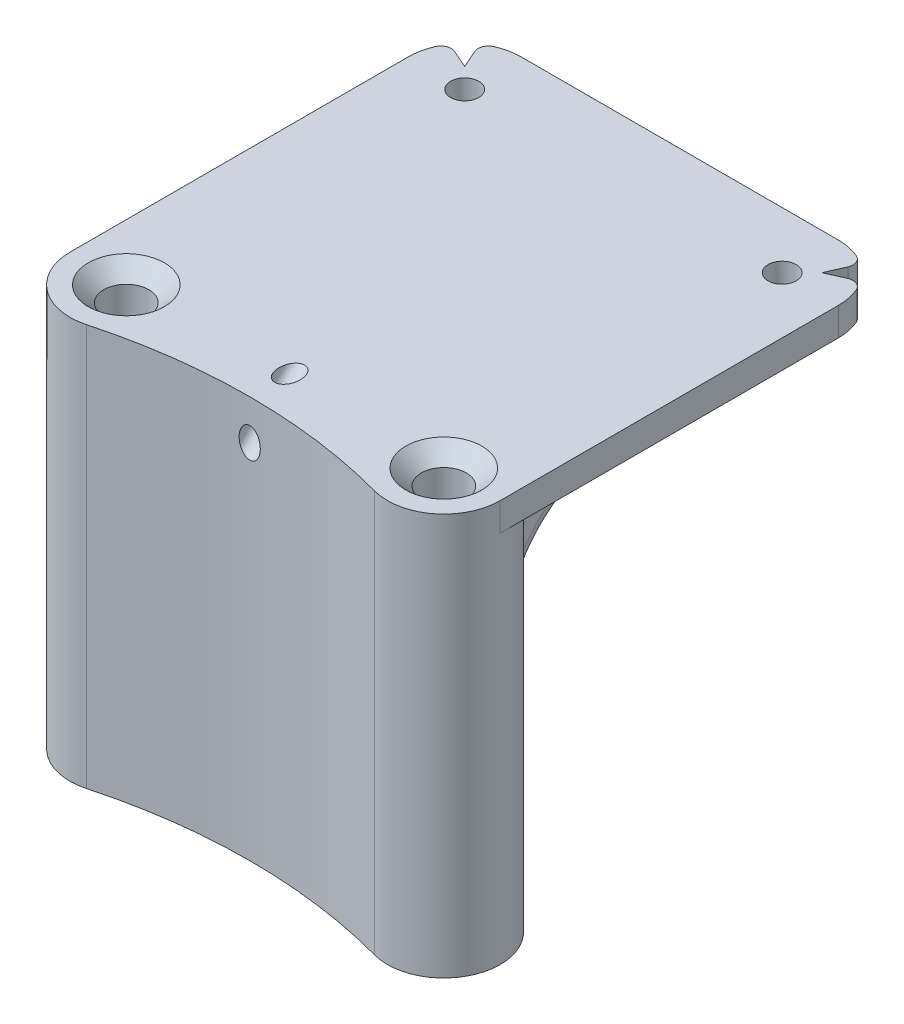
SolidWorks part; units mm, degrees
ref_plane "前视基准面" through (0, 0, 0) normal (0, 0, 1) x (1, 0, 0)
ref_plane "上视基准面" through (0, 0, 0) normal (0, 1, 0) x (1, 0, 0)
ref_plane "右视基准面" through (0, 0, 0) normal (1, 0, 0) x (0, 0, -1)
other "Configuration Table"
sketch "草图2" plane through (0, 0, 0) normal (0, 1, 0) x (1, 0, 0)
  line L0 (0, 41.5125) -> (0, -41.5125) construction
  line L1 (-11.26, 0) -> (11.26, 0) construction
  arc A0 (-10.2129, 3.8605) -> (-10.2129, -3.8605) centre (-11.26, 0) ccw
  arc A1 (10.2129, 3.8605) -> (10.2129, -3.8605) centre (11.26, 0) cw
  arc A2 (-10.2129, -3.8605) -> (10.2129, -3.8605) centre (0, -41.5125) cw
  arc A3 (-10.2129, 3.8605) -> (10.2129, 3.8605) centre (0, 41.5125) ccw
  point P1 (-2.8347, -1.5911)
  point P4 (0, -26.6736)
  point P5 (0, -26.6736)
  point P10 (0, 0)
  point P12 (-8.124, -6.199)
  point P13 (0, 0)
  point P14 (0, -13.3421)
  point P15 (6.0787, -3.7192)
  point P16 (-6.0424, -3.1641)
  point P17 (0, -18.5214)
  point P18 (0, -17.4888)
  point P19 (0, 0)
  point P20 (0, 0)
  point P21 (0, 0)
  point P22 (0, 0)
  point P25 (0, -26.6736)
  point P26 (0, -2.5)
  dimension "D1" = 4
  dimension "D2" = 22.52
  dimension "D3" = 2.5
extrude "凸台-拉伸1" add sketch "草图2" along normal blind 28.5
sketch "草图3" plane through (0, 0, 0) normal (0, -1, 0) x (1, 0, 0)
  line L3 (0, 2.5) -> (0, -2.5) construction
  line L5 (-15.26, 0) -> (15.26, 0) construction
  circle A0 centre (-11.26, 0) radius 1.6
  arc A2 (-10.2129, 3.8605) -> (10.2129, 3.8605) centre (0, 41.5125) ccw construction
  arc A3 (10.2129, -3.8605) -> (-10.2129, -3.8605) centre (0, -41.5125) ccw construction
  arc A4 (-10.2129, 3.8605) -> (-10.2129, -3.8605) centre (-11.26, 0) ccw construction
  arc A5 (10.2129, -3.8605) -> (10.2129, 3.8605) centre (11.26, 0) ccw construction
  circle A6 centre (11.26, 0) radius 1.6
  point P2 (0, 0)
  dimension "D1" = 3.2
extrude "切除-拉伸1" cut sketch "草图3" against normal through all
sketch "草图4" plane through (0, 28.5, 0) normal (0, 1, 0) x (1, 0, 0)
  line L0 (-11.26, 0) -> (11.26, 0) construction
  line L1 (0, -2.5) -> (0, 2.5) construction
  line L2 (-15.26, 0) -> (-15.26, 28)
  line L3 (-15.26, 28) -> (15.26, 28)
  line L5 (15.26, 0) -> (15.26, 28)
  arc A0 (10.2129, -3.8605) -> (-10.2129, -3.8605) centre (0, -41.5125) ccw construction
  arc A1 (-10.2129, 3.8605) -> (10.2129, 3.8605) centre (0, 41.5125) ccw construction
  arc A2 (-10.2129, 3.8605) -> (-10.2129, -3.8605) centre (-11.26, 0) ccw construction
  arc A3 (10.2129, -3.8605) -> (10.2129, 3.8605) centre (11.26, 0) ccw construction
  arc A7 (-15.26, 0) -> (-10.2129, 3.8605) centre (-11.26, 0) cw
  arc A8 (-10.2129, 3.8605) -> (10.2129, 3.8605) centre (0, 41.5125) ccw
  arc A9 (10.2129, 3.8605) -> (15.26, 0) centre (11.26, 0) cw
  dimension "D1" = 28
extrude "凸台-拉伸2" add sketch "草图4" against normal blind 2
sketch "草图5" plane through (0, 26.5, 0) normal (0, -1, 0) x (1, 0, 0)
  line L0 (15.26, -28) -> (-15.26, -28) construction
  line L1 (-10.26, -26) -> (-5.76, -26)
  line L2 (-10.26, -26) -> (-10.26, -28)
  line L3 (-10.26, -28) -> (-5.76, -28)
  line L4 (-5.76, -26) -> (-5.76, -28)
  line L5 (-15.26, -28) -> (-15.26, 0) construction
  dimension "D1" = 2
  dimension "D2" = 4.5
  dimension "D3" = 5
extrude "凸台-拉伸3" add sketch "草图5" along normal blind 15.5
sketch "草图6" plane through (0, 0, -28) normal (0, 0, -1) x (-1, 0, 0)
  line L0 (10.26, 11) -> (5.76, 11) construction
  line L1 (5.76, 11) -> (5.76, 26.5) construction
  circle A0 centre (7.81, 17) radius 1.5
  dimension "D1" = 3
  dimension "D2" = 6
  dimension "D3" = 2.05
extrude "切除-拉伸2" cut sketch "草图6" against normal up to next
chamfer "倒角1" distance 1.1 angle 45 2 edges at (-11.26, 28.5, -1.6) (11.26, 28.5, 1.6)
fillet "圆角1" radius 1 1 edges at (-10.26, 11, -27)
fillet "圆角3" radius 4 2 edges at (15.26, 27.5, -28) (-15.26, 27.5, -28)
fillet "圆角4" radius 5 1 edges at (-10.26, 26.5, -27)
ref_plane "基准面1" through (0, 28.25, -28.25) normal (0, 0.7071, -0.7071) x (-1, 0, 0)
sketch "草图9" plane through (0, 28.25, -28.25) normal (0, 0.7071, -0.7071) x (-1, 0, 0)
  circle A0 centre (0, 19.9203) radius 0.75
  ellipse E0 centre (0, 49.5063) end of major axis (-39.0125, 49.5063) minor radius 27.586 (-10.2129, 22.8823) -> (10.2129, 22.8823) ccw construction
  point P2 (0, 15.9481)
  point P10 (0, 0)
  dimension "D1" = 1.5
  dimension "D2" = 2
extrude "切除-拉伸4" cut sketch "草图9" against normal through all
sketch "草图10" plane through (0, 28.5, 0) normal (0, 1, 0) x (1, 0, 0)
  line L0 (0, 28) -> (0, -2.5) construction
  line L1 (11.26, 28) -> (-11.26, 28) construction
  line L2 (-11.26, 24) -> (-14.0884, 26.8284) construction
  line L3 (-12.6742, 25.4142) -> (-13.5079, 27.3086)
  line L4 (-12.6742, 25.4142) -> (-14.5686, 26.2479)
  line L5 (12.6742, 25.4142) -> (13.5079, 27.3086)
  line L6 (12.6742, 25.4142) -> (14.5686, 26.2479)
  arc A0 (10.2129, -3.8605) -> (-10.2129, -3.8605) centre (0, -41.5125) ccw construction
  circle A1 centre (-11.26, 24) radius 1
  circle A2 centre (11.26, 24) radius 1
  arc A3 (-11.26, 28) -> (-15.26, 24) centre (-11.26, 24) ccw construction
  arc A4 (-13.5079, 27.3086) -> (-14.5686, 26.2479) centre (-12.6742, 25.4142) ccw
  arc A5 (13.5079, 27.3086) -> (14.5686, 26.2479) centre (12.6742, 25.4142) cw
  point P19 (0, 0)
  dimension "D1" = 2
  dimension "D2" = 45
  dimension "D3" = 2
  dimension "D4" = 1.5
extrude "切除-拉伸5" cut sketch "草图10" against normal through all
fillet "圆角6" radius 0.75 4 edges at (13.5079, 27.5, -27.3086) (14.5686, 27.5, -26.2479) (-13.5079, 27.3415, -27.3086) (-14.5686, 27.476, -26.2479)
sketch "草图11" plane through (0, 26.5, 0) normal (0, -1, 0) x (1, 0, 0)
  line L0 (11.26, 0) -> (11.26, -4) construction
  line L2 (10.26, -3.873) -> (10.26, -22)
  line L4 (12.26, -3.873) -> (12.26, -22)
  line L5 (10.26, -22) -> (12.26, -22)
  arc A3 (12.26, -3.873) -> (10.26, -3.873) centre (11.26, 0) cw
  arc A6 (10.2129, -3.8605) -> (10.2129, 3.8605) centre (11.26, 0) ccw construction
  point P4 (11.26, -4)
  dimension "D2" = 18
  dimension "D1" = 2
extrude "凸台-拉伸4" add sketch "草图11" along normal blind 2
fillet "圆角7" radius 8 1 edges at (11.26, 24.5, -4)
fillet "圆角10" radius 2 1 edges at (-5.76, 26.5, -27)
fillet "圆角11" radius 1 6 edges at (10.26, 22.5082, -6.643) (12.26, 21.3789, -5.5709) (10.26, 26.5, -12.9365) (12.26, 26.5, -12.9365) (10.26, 24.5, -16.9791) (12.26, 24.5, -16.9791)
